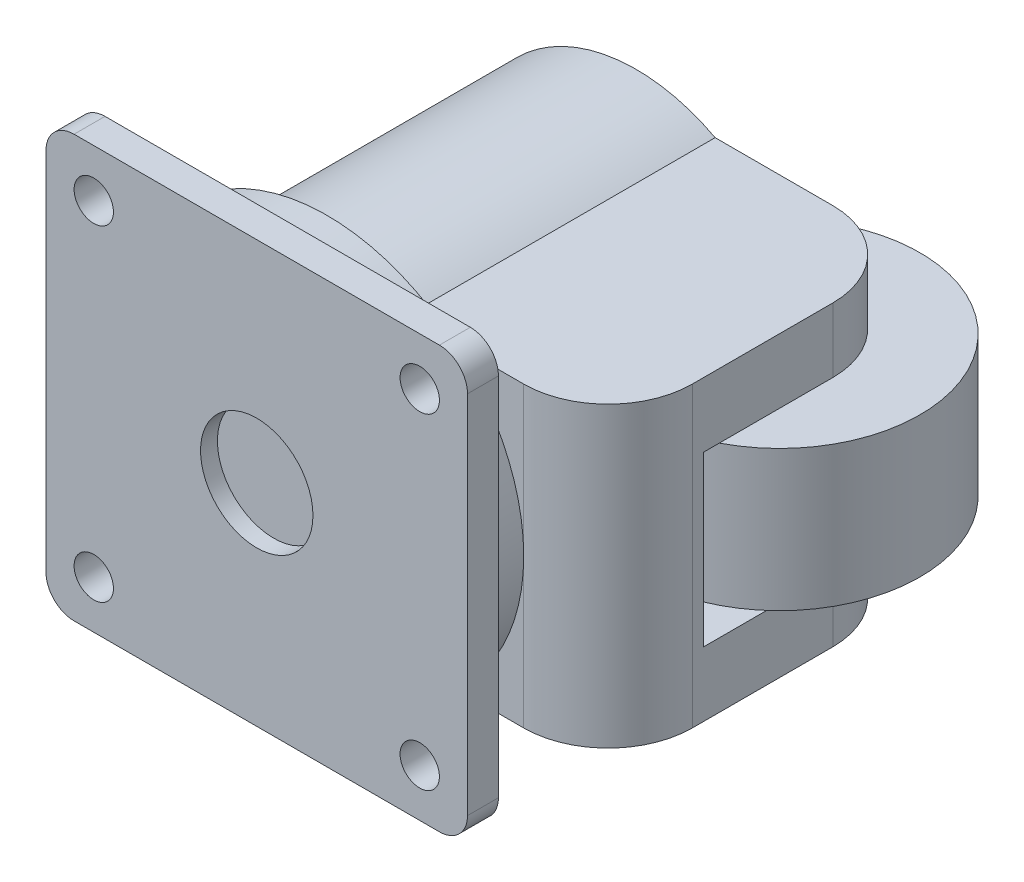
SolidWorks part; units mm, degrees
material "尼龙 6/10"
ref_plane "前视基准面" through (0, 0, 0) normal (0, 0, 1) x (1, 0, 0)
ref_plane "上视基准面" through (0, 0, 0) normal (0, 1, 0) x (1, 0, 0)
ref_plane "右视基准面" through (0, 0, 0) normal (1, 0, 0) x (0, 0, -1)
sketch "草图1" plane through (0, 0, 0) normal (0, 0, 1) x (1, 0, 0)
  line L0 (0, 0) -> (67.8853, 0) construction
  line L1 (0, 0) -> (0, 60.5683) construction
  line L3 (-37.5, 37.5) -> (37.5, 37.5)
  line L4 (-37.5, 37.5) -> (-37.5, -37.5)
  line L5 (-37.5, -37.5) -> (37.5, -37.5)
  line L6 (37.5, 37.5) -> (37.5, -37.5)
  dimension "D1" = 75
  dimension "D2" = 75
extrude "拉伸1" add sketch "草图1" along normal blind 5.5
fillet "圆角1" radius 5 4 edges at (-37.5, -37.5, 2.75) (37.5, -37.5, 2.75) (37.5, 37.5, 2.75) (-37.5, 37.5, 2.75)
sketch "草图2" plane through (0, 0, 5.5) normal (0, 0, 1) x (1, 0, 0)
  circle A0 centre (-29, 29) radius 3.5
  dimension "D1" = 7
  dimension "D2" = 29
  dimension "D3" = 29
extrude "切除-拉伸1" cut sketch "草图2" against normal through all
ref_axis "基准轴1" through (0, 0, -0.275) along (0, 0, 1)
pattern_circular "阵列(圆周)1" count 4 over 360 about axis through (0, 0, -0.275) along (0, 0, 1) of "切除-拉伸1"
sketch "草图3" plane through (0, 0, 5.5) normal (0, 0, 1) x (1, 0, 0)
  circle A0 centre (0, 0) radius 10
  dimension "D1" = 20
extrude "切除-拉伸2" cut sketch "草图3" against normal blind 3
sketch "草图4" plane through (0, 0, 0) normal (0, 0, -1) x (-1, 0, 0)
  circle A4 centre (0, 0) radius 35
  dimension "D1" = 70
extrude "拉伸2" add sketch "草图4" along normal blind 7
sketch "草图5" plane through (0, 0, -7) normal (0, 0, -1) x (-1, 0, 0)
  circle A2 centre (0, 0) radius 30
  circle A3 centre (0, 0) radius 30
  dimension "D1" = 5
extrude "拉伸3" add sketch "草图5" along normal blind 55
sketch "草图6" plane through (0, 0, 0) normal (0, 1, 0) x (1, 0, 0)
  line L0 (0, 0) -> (0, 62) construction
  line L1 (30, 62) -> (-30, 62) construction
  line L3 (0, 62) -> (50, 62)
  line L4 (0, 62) -> (0, 7)
  line L5 (0, 7) -> (50, 7)
  line L6 (50, 62) -> (50, 7)
  dimension "D1" = 50
extrude "拉伸4" add sketch "草图6" along normal mid plane 53
fillet "圆角2" radius 15 1 edges at (50, 0, -7)
sketch "草图7" plane through (50, 0, 0) normal (1, 0, 0) x (0, 0, -1)
  line L0 (0, 0) -> (62, 0) construction
  line L1 (62, 26.5) -> (62, -26.5) construction
  line L3 (62, 15) -> (24, 15)
  line L4 (62, 15) -> (62, -15)
  line L5 (62, -15) -> (24, -15)
  line L6 (24, 15) -> (24, -15)
  dimension "D1" = 30
  dimension "D2" = 38
extrude "切除-拉伸3" cut sketch "草图7" against normal through all
sketch "草图8" plane through (0, 26.5, 0) normal (0, 1, 0) x (1, 0, 0)
  line L0 (0, 0) -> (0, 62) construction
  line L1 (14.0624, 62) -> (-25.9808, 62) construction
  line L2 (32.5, -5.5) -> (-32.5, -5.5) construction
  circle A0 centre (36, 51.5) radius 2.5
  dimension "D1" = 5
  dimension "D2" = 36
  dimension "D3" = 57
sketch "草图9" plane through (0, 0, 0) normal (0, 1, 0) x (1, 0, 0)
  line L0 (0, 0) -> (0, 62) construction
  line L1 (14.0624, 62) -> (-25.9808, 62) construction
  line L2 (32.5, -5.5) -> (-32.5, -5.5) construction
  circle A0 centre (36, 51.5) radius 25
  dimension "D1" = 50
  dimension "D2" = 36
  dimension "D3" = 57
extrude "拉伸5" add sketch "草图9" along normal mid plane 25
extrude "拉伸6" add sketch "草图8" against normal up to surface (53 mm away) up to face at (31.5158, -26.5, -27.3156)
fillet "圆角3" radius 15 2 edges at (50, -20.75, -62) (50, 20.75, -62)
